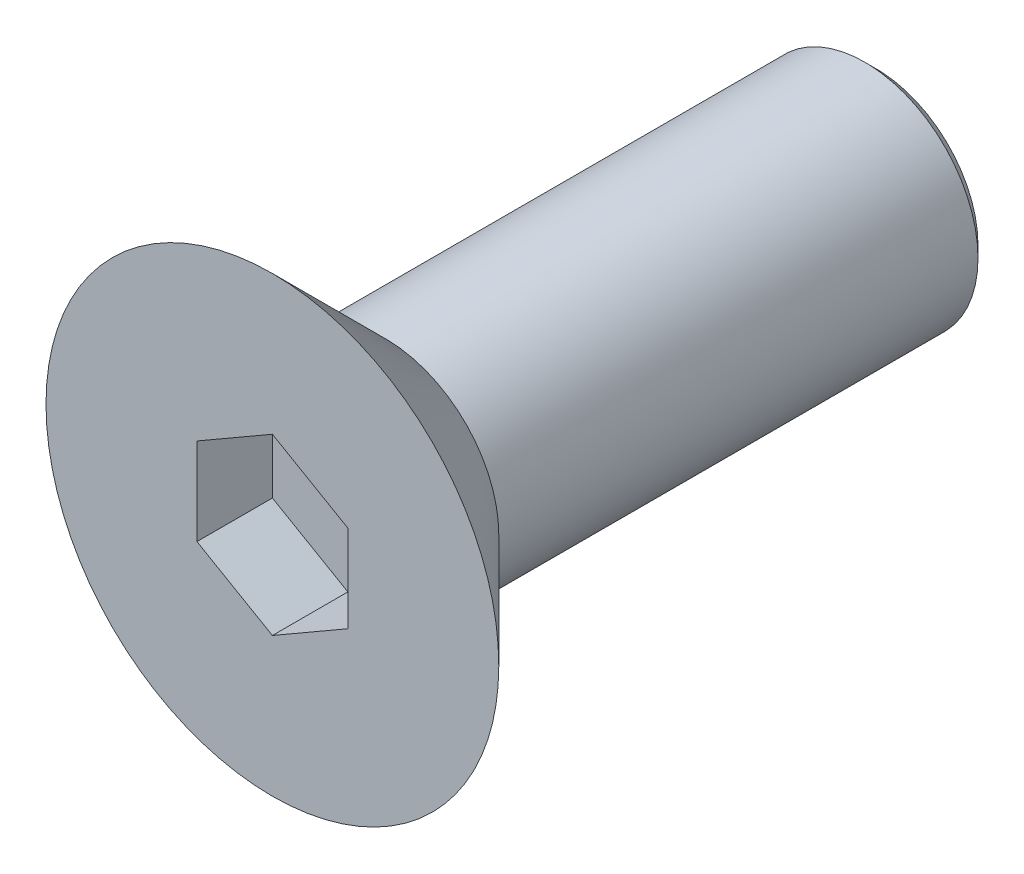
SolidWorks part; units mm, degrees
ref_plane "Front Plane" through (0, 0, 0) normal (0, 0, 1) x (1, 0, 0)
ref_plane "Top Plane" through (0, 0, 0) normal (0, 1, 0) x (1, 0, 0)
ref_plane "Right Plane" through (0, 0, 0) normal (1, 0, 0) x (0, 0, -1)
sketch "Sketch1" plane through (0, 0, 0) normal (0, 0, 1) x (1, 0, 0)
  circle A0 centre (0, 0) radius 6
  dimension "D1" = 12
extrude "Boss-Extrude1" add sketch "Sketch1" along normal blind 3
sketch "Sketch2" plane through (0, 0, 0) normal (0, 0, -1) x (-1, 0, 0)
  circle A0 centre (0, 0) radius 3
  dimension "D1" = 6
extrude "Boss-Extrude2" add sketch "Sketch2" along normal blind 13
chamfer "Chamfer1" distance 0.3 angle 45 1 edges at (-3, 0, -13)
sketch "Sketch3" plane through (0, 0, 3) normal (0, 0, 1) x (1, 0, 0)
  line L1 (0, 2.3094) -> (-2, 1.1547)
  line L2 (-2, 1.1547) -> (-2, -1.1547)
  line L3 (-2, -1.1547) -> (0, -2.3094)
  line L4 (0, -2.3094) -> (2, -1.1547)
  line L5 (2, -1.1547) -> (2, 1.1547)
  line L6 (2, 1.1547) -> (0, 2.3094)
  circle A0 centre (0, 0) radius 2 construction
  dimension "D1" = 4
extrude "Cut-Extrude1" cut sketch "Sketch3" against normal blind 2
chamfer "Chamfer2" distance 3 angle 45 1 edges at (6, 0, 0)
